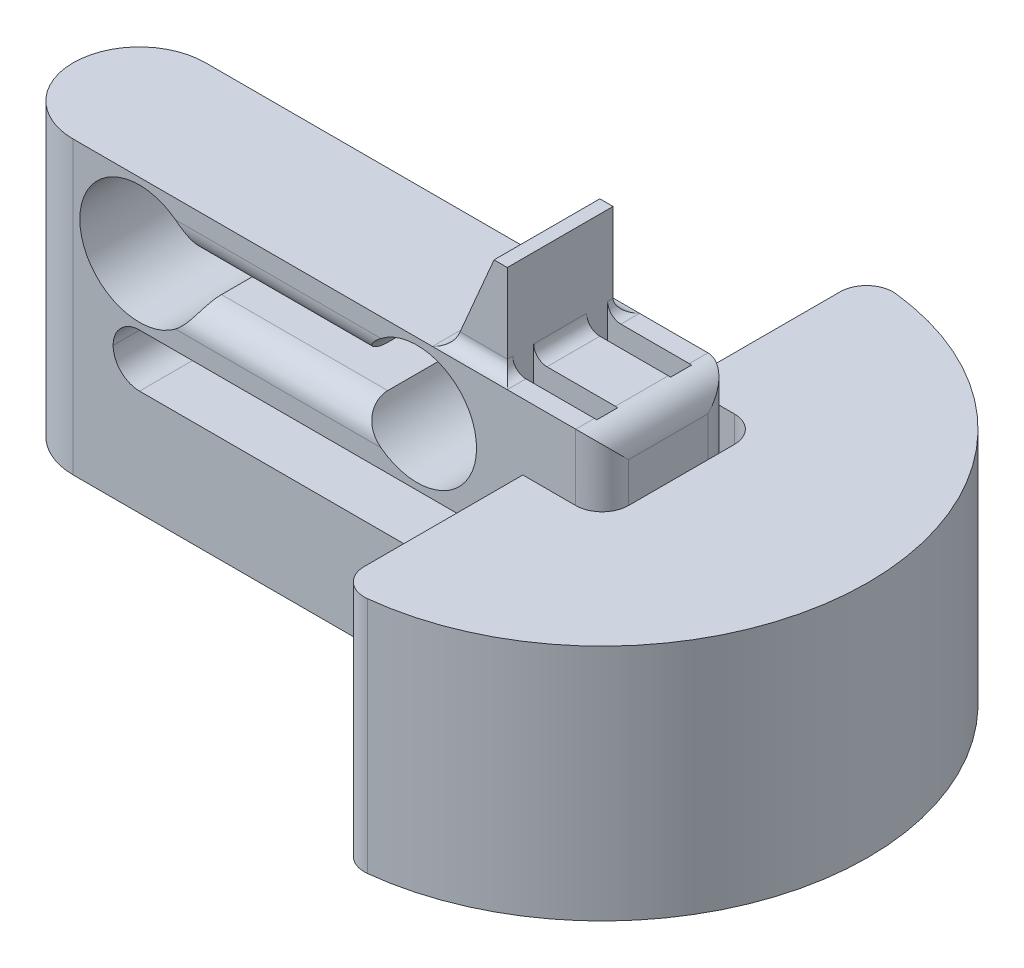
SolidWorks part; units mm, degrees
material "PEBA"
ref_plane "Front Plane" through (0, 0, 0) normal (0, 0, 1) x (1, 0, 0)
ref_plane "Top Plane" through (0, 0, 0) normal (0, 1, 0) x (1, 0, 0)
ref_plane "Right Plane" through (0, 0, 0) normal (1, 0, 0) x (0, 0, -1)
other "Center of Mass"
sketch "Sketch1" plane through (0, 0, 0) normal (0, 0, 1) x (1, 0, 0)
  line L0 (5, 0) -> (0, 0)
  line L1 (0, 0) -> (-5, 0)
  line L2 (-5, 0) -> (-35, 0)
  line L3 (5, 0) -> (5, -10)
  line L4 (5, -10) -> (-5, -10)
  line L5 (-5, -10) -> (-31.9826, -10)
  line L6 (-35, 0) -> (-40, 0)
  line L7 (-26.8791, -3.4207) -> (-11.5008, -3.4207)
  line L8 (-26.8791, -3.4207) -> (-26.8791, -6.5793)
  line L9 (-26.8791, -6.5793) -> (-11.5008, -6.5793)
  line L10 (-11.5008, -3.4207) -> (-11.5008, -6.5793)
  line L11 (-26.8791, -3.4207) -> (-11.5008, -6.5793) construction
  line L12 (-26.8791, -6.5793) -> (-11.5008, -3.4207) construction
  line L13 (-40, 0) -> (-40, -14)
  line L14 (-40, -14) -> (-31.9826, -14)
  line L15 (-31.9826, -14) -> (-31.9826, -10)
  circle A0 centre (-30, -5) radius 4.5
  circle A1 centre (-9, -5) radius 4.5
  point P12 (-19.1899, -5)
  dimension "D5" = 5
  dimension "D6" = 5
  dimension "D7" = 9
  dimension "D8" = 9
  dimension "D1" = 5
  dimension "D2" = 5
  dimension "D3" = 30
  dimension "D4" = 10
  dimension "D9" = 4
  dimension "D10" = 40
  dimension "D11" = 14
extrude "Boss-Extrude1" add sketch "Sketch1" along normal blind 5 and the other way blind 5 contours L14 L15 L5 L4 L3 L0 L1 L2 L6 L13 A1 L9 A0 L7 region at (4.5287, -5, 0)
sketch "Sketch2" plane through (0, 0, 0) normal (0, 1, 0) x (1, 0, 0)
  line L1 (-3.175, -3.5875) -> (3.175, -3.5875)
  line L2 (-3.175, -3.5875) -> (-3.175, -2)
  line L3 (-3.175, -2) -> (3.175, -2)
  line L4 (3.175, -3.5875) -> (3.175, -2)
  line L5 (0, -2) -> (0, -3.5875) construction
  line L6 (5, 5) -> (-40, 5) construction
  line L7 (0, 0) -> (3.6499, 0) construction
  line L8 (3.175, 3.5875) -> (3.175, 2)
  line L9 (-3.175, 3.5875) -> (3.175, 3.5875)
  line L10 (-3.175, 3.5875) -> (-3.175, 2)
  line L11 (-3.175, 2) -> (3.175, 2)
  dimension "D1" = 6.35
  dimension "D2" = 7
  dimension "D3" = 1.5875
extrude "Cut-Extrude1" cut sketch "Sketch2" against normal blind 5
sketch "Sketch3" plane through (0, 0, 0) normal (0, 1, 0) x (1, 0, 0)
  line L0 (5, -5) -> (-40, -5) construction
  line L1 (-40, 5) -> (5.8816, 5)
  line L2 (-40, 5) -> (-40, -5)
  line L3 (-40, -5) -> (5.8816, -5)
  line L4 (5.8816, 5) -> (5.8816, -5)
  line L6 (-44.7352, 22.5342) -> (0, 22.5342)
  line L7 (-44.7352, 22.5342) -> (-44.7352, -27.8282)
  line L8 (-44.7352, -27.8282) -> (0, -27.8282)
  line L9 (0, 22.5342) -> (0, -27.8282)
  circle A0 centre (0, 0) radius 20.1
  dimension "D1" = 40.2
extrude "Boss-Extrude2" add sketch "Sketch3" against normal blind 8 from offset 14 contours L9 A0 L1 L4 L3 | L1 L9 L3 L4 | L1 A0 L3 L9 | A0 L1 L2 L3 region at (-29.9445, 0, 0) region at (-9.9463, 0, 0) region at (9.1017, 0, 0) region at (2.9408, 0, 0) offset against normal yes
sketch "Sketch4" plane through (0, -14, 0) normal (0, 1, 0) x (1, 0, 0)
  line L0 (5, 5) -> (-40, 5) construction
  line L1 (0, 20.1) -> (46.8504, 20.1)
  line L2 (0, 20.1) -> (0, -35.9681)
  line L3 (0, -35.9681) -> (46.8504, -35.9681)
  line L4 (46.8504, 20.1) -> (46.8504, -35.9681)
  line L5 (6, 6) -> (-6.1468, 6)
  line L6 (6, 6) -> (6, -6)
  line L7 (6, -6) -> (-6.1468, -6)
  line L8 (-6.1468, 6) -> (-6.1468, -6)
  line L9 (5, -5) -> (-40, -5) construction
  line L10 (5, 5) -> (5, -5) construction
  circle A0 centre (0, 0) radius 20.1
  arc A1 (0, -20.1) -> (0, 20.1) centre (0, 0) ccw construction
  arc M8 (0, -20.1) -> (0, 20.1) centre (0, 0) ccw
  line M9 (0, 20.1) -> (0, 5)
  dimension "D1" = 1
  dimension "D2" = 1
  dimension "D3" = 1
extrude "Boss-Extrude3" add sketch "Sketch4" along normal blind 10 contours L6 L7 L2 L5 M8 M9 region at (9.2385, -14, 0)
fillet "Fillet2" radius 5 2 edges at (-40, -11, -5) (-40, -11, 5)
fillet "Fillet6" radius 2 5 edges at (6, -9, -6) (6, -9, 6) (5, -5, -5) (5, -5, 5) (5, 0, 0)
fillet "Fillet3" radius 2 8 edges at (-19.5, -3.4207, -5) (-19.5, -6.5793, -5) (-19.5, -6.5793, 5) (-19.5, -3.4207, 5) (-31.9826, -10, 0) (-31.9826, -14, 0) (0, -13, -20.1) (0, -13, 20.1)
sketch "Sketch5" plane through (0, -22, 0) normal (0, -1, 0) x (1, 0, 0)
  line L0 (-35, 0) -> (-12, 0) construction
  line L1 (-35, 3.25) -> (-12, 3.25)
  line L2 (-35, -3.25) -> (-12, -3.25)
  line L3 (-6, 0) -> (0, 0) construction
  line L4 (-7.5, 1.5) -> (-4.5, 1.5)
  line L5 (-7.5, 1.5) -> (-7.5, -1.5)
  line L6 (-7.5, -1.5) -> (-4.5, -1.5)
  line L7 (-4.5, 1.5) -> (-4.5, -1.5)
  line L8 (-7.5, 1.5) -> (-4.5, -1.5) construction
  line L9 (-7.5, -1.5) -> (-4.5, 1.5) construction
  line L10 (4.5, 1.5) -> (7.5, 1.5)
  line L11 (4.5, 1.5) -> (4.5, -1.5)
  line L12 (4.5, -1.5) -> (7.5, -1.5)
  line L13 (7.5, 1.5) -> (7.5, -1.5)
  line L14 (4.5, 1.5) -> (7.5, -1.5) construction
  line L15 (4.5, -1.5) -> (7.5, 1.5) construction
  line L16 (0, 0) -> (6, 0) construction
  arc A0 (-35, 3.25) -> (-35, -3.25) centre (-35, 0) ccw
  arc A1 (-12, -3.25) -> (-12, 3.25) centre (-12, 0) ccw
  circle A3 centre (0, 0) radius 1.5
  point P3 (-23.5, 0)
  point P8 (-6, 0)
  point P13 (6, 0)
  dimension "D3" = 3
  dimension "D9" = 3
  dimension "D1" = 35
  dimension "D2" = 12
  dimension "D4" = 3
  dimension "D5" = 0
  dimension "D6" = 12
  dimension "D7" = 3
extrude "Cut-Extrude2" cut sketch "Sketch5" against normal blind 4
fillet "Fillet4" radius 1 6 edges at (-23.5, -18, 3.25) (-8.75, -18, 0) (-23.5, -18, -3.25) (-38.25, -18, 0) (0, -18, -5) (0, -18, 5)
sketch "Sketch6" plane through (0, -22, 0) normal (0, -1, 0) x (1, 0, 0)
  circle A0 centre (-35, 0) radius 3.25
extrude "Cut-Extrude3" cut sketch "Sketch6" against normal blind 5
sketch "Sketch7" plane through (0, 0, 0) normal (0, 1, 0) x (1, 0, 0)
  circle A0 centre (0, 0) radius 2.5
  dimension "D1" = 5
extrude "Boss-Extrude4" add sketch "Sketch7" along normal blind 3.7 from surface starting at face at (-4.0723, -14, 0)
sketch "Sketch9" plane through (0, -10.3, 0) normal (0, 1, 0) x (1, 0, 0)
  circle A0 centre (0, 0) radius 1.45
  dimension "D1" = 2.9
extrude "Cut-Extrude4" cut sketch "Sketch9" against normal blind 4.6 contours A0
fillet "Fillet5" radius 2.5 1 edges at (0, -14, 2.5)
sketch "Sketch10" plane through (0, 0, 0) normal (0, 1, 0) x (1, 0, 0)
  line L0 (-7.175, 0) -> (-3.175, 0) construction
  line L1 (-3.175, 4) -> (-7.175, 4)
  line L2 (-3.175, 4) -> (-3.175, -4)
  line L3 (-3.175, -4) -> (-7.175, -4)
  line L4 (-7.175, 4) -> (-7.175, -4)
  line L6 (-3.175, -2) -> (-3.175, -3.5875) construction
  dimension "D1" = 8
  dimension "D2" = 4
extrude "Boss-Extrude5" add sketch "Sketch10" along normal blind 7
sketch "Sketch11" plane through (0, 0, 4) normal (0, 0, 1) x (1, 0, 0)
  line L0 (-7.175, 0) -> (-7.175, 7)
  line L1 (-7.175, 7) -> (-3.175, 7) construction
  line L2 (-7.175, 7) -> (-7.175, 0) construction
  line L3 (-7.175, 7) -> (-4.175, 7)
  line L4 (-4.175, 7) -> (-7.175, 0)
  dimension "D1" = 3
extrude "Cut-Extrude5" cut sketch "Sketch11" against normal up to next contours L4 L0 L3
fillet "Fillet7" radius 1 6 edges at (-3.175, 0, 3.7938) (-3.175, 0, -3.7938) (-5.175, 0, -4) (-5.175, 0, 4) (-7.175, 0, 0) (-3.175, 0, 0)
other "Center of Mass Reference Point1"
